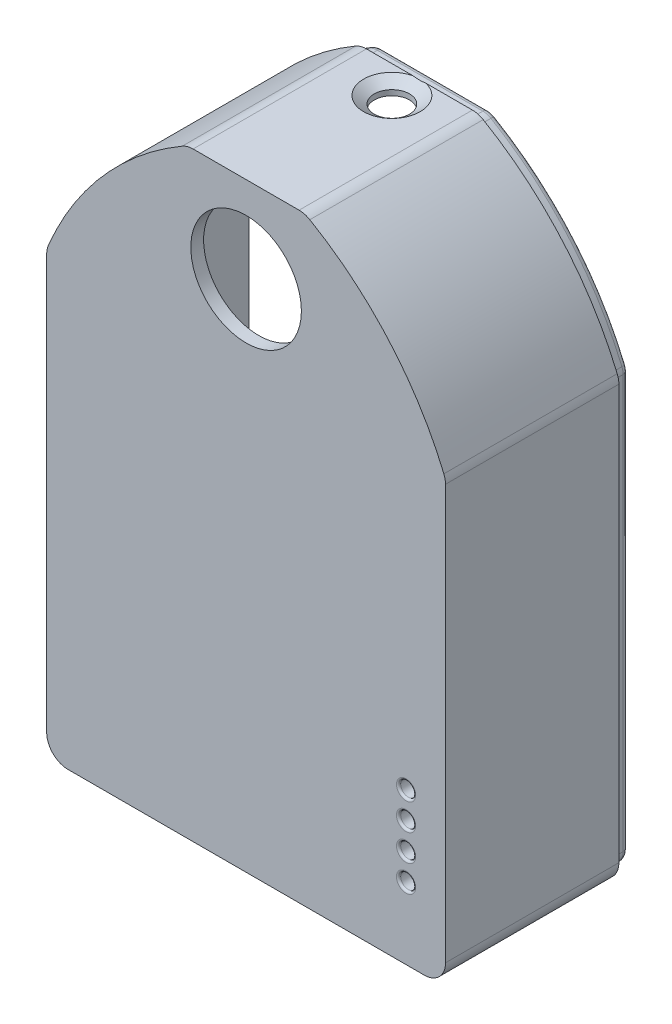
SolidWorks part; units mm, degrees
ref_plane "Front Plane" through (0, 0, 0) normal (0, 0, 1) x (1, 0, 0)
ref_plane "Top Plane" through (0, 0, 0) normal (0, 1, 0) x (1, 0, 0)
ref_plane "Right Plane" through (0, 0, 0) normal (1, 0, 0) x (0, 0, -1)
sketch "Sketch1" plane through (0, 0, 0) normal (0, 0, 1) x (1, 0, 0)
  circle A0 centre (-22.9417, 27.5534) radius 1.85
  circle A1 centre (-22.9417, -28.0566) radius 1.85
  circle A2 centre (30, 35.5) radius 1.1
  circle A3 centre (30, -35.5) radius 1.1
  dimension "D1" = 3.7
  dimension "D2" = 3.7
extrude "Extrude-Thin1" add sketch "Sketch1" along normal blind 5 thin thin type one direction wall 2.8
sketch "Sketch3" plane through (0, 0, 5) normal (0, 0, 1) x (1, 0, 0)
  line L0 (-37.4, -41.9) -> (37.4, -41.9)
  line L1 (37.4, -41.9) -> (37.4, 70.61)
  line L2 (37.4, 70.61) -> (-37.4, 70.61)
  line L3 (-37.4, 70.61) -> (-37.4, -41.9)
  line L4 (0, 70.61) -> (0, 40.61) construction
  line L5 (-37.4, 40.61) -> (37.4, 40.61) construction
  line L6 (-11, 70.61) -> (-11, 40.61) construction
  arc A0 (-37.4, 40.61) -> (-11, 70.61) centre (18.2718, 18.2348) cw
  arc A1 (37.4, 40.61) -> (11, 70.61) centre (-18.2718, 18.2348) ccw
  point P15 (0, 70.61)
  circle M7 centre (-22.9417, 27.5534) radius 4.65
  circle M8 centre (-22.9417, 27.5534) radius 1.85
  dimension "D6" = 60
  dimension "D1" = 2.4
  dimension "D2" = 3.4
  dimension "D3" = 3.4
  dimension "D4" = 2.4
  dimension "D5" = 11
  dimension "D7" = 30
extrude "Boss-Extrude2" add sketch "Sketch3" along normal blind 2.4 contours L1 A1 L2 A0 L3 L0 M7 | M7 M8 | M8 region at (0.2014, 10.5056, 5) region at (-27.4601, 27.5534, 5) region at (-22.9417, 27.5534, 5)
sketch "Sketch4" plane through (0, 0, 5) normal (0, 0, -1) x (-1, 0, 0)
  line L4 (-37.4, 40.61) -> (-37.4, -41.9)
  line L5 (-37.4, -41.9) -> (37.4, -41.9)
  line L6 (37.4, -41.9) -> (37.4, 40.61)
  line L7 (11, 70.61) -> (-11, 70.61)
  line L8 (-37.4, 40.61) -> (-37.4, -41.9)
  line L9 (-37.4, -41.9) -> (37.4, -41.9)
  line L10 (37.4, -41.9) -> (37.4, 40.61)
  line L11 (11, 70.61) -> (-11, 70.61)
  arc A2 (37.4, 40.61) -> (11, 70.61) centre (-18.2718, 18.2348) ccw
  arc A3 (-11, 70.61) -> (-37.4, 40.61) centre (18.2718, 18.2348) ccw
  arc A4 (37.4, 40.61) -> (11, 70.61) centre (-18.2718, 18.2348) ccw
  arc A5 (-11, 70.61) -> (-37.4, 40.61) centre (18.2718, 18.2348) ccw
  dimension "D1" = 0
extrude "Extrude-Thin2" add sketch "Sketch4" along normal up to surface (30.11 mm away) thin thin type one direction reverse wall 2.4
sketch "Sketch5" plane through (0, 0, 7.4) normal (0, 0, 1) x (1, 0, 0)
  circle A0 centre (0, 54.4311) radius 10.3689
extrude "Cut-Extrude1" cut sketch "Sketch5" against normal blind 2.4
sketch "Sketch6" plane through (0, 0, -25.11) normal (0, 0, -1) x (-1, 0, 0)
  line L0 (35, -39.5) -> (-35, -39.5) construction
  line L1 (35, 40.1408) -> (35, -39.5) construction
  line L2 (-10.368, 68.21) -> (10.368, 68.21) construction
  line L3 (-35, -39.5) -> (-35, 40.1408) construction
  line L4 (35, -39.5) -> (-35, -39.5)
  line L5 (35, 40.1408) -> (35, -39.5)
  line L6 (-10.368, 68.21) -> (10.368, 68.21)
  line L7 (-35, -39.5) -> (-35, 40.1408)
  arc A0 (35, 40.1408) -> (10.368, 68.21) centre (-18.2718, 18.2348) ccw construction
  arc A1 (-10.368, 68.21) -> (-35, 40.1408) centre (18.2718, 18.2348) ccw construction
  arc A2 (35, 40.1408) -> (10.368, 68.21) centre (-18.2718, 18.2348) ccw
  arc A3 (-10.368, 68.21) -> (-35, 40.1408) centre (18.2718, 18.2348) ccw
extrude "Extrude-Thin3" add sketch "Sketch6" along normal up to surface (3 mm away) thin thin type one direction wall 1.2
sketch "Sketch7" plane through (0, -41.9, 0) normal (0, -1, 0) x (1, 0, 0)
  line L0 (-34, -1.51) -> (34, -1.51) construction
  line L1 (-6.0348, -7.6386) -> (3.7281, -7.6386)
  line L2 (-6.0348, -7.6386) -> (-6.0348, -2.31)
  line L3 (-6.0348, -2.31) -> (3.7281, -2.31)
  line L4 (3.7281, -7.6386) -> (3.7281, -2.31)
  line L17 (18, -0.615) -> (21.22, -0.615)
  line L18 (14.78, -0.615) -> (18, -0.615)
  line L19 (12.73, 2.095) -> (12.73, 1.435)
  line L20 (18, 4.145) -> (14.78, 4.145)
  line L21 (21.22, 4.145) -> (18, 4.145)
  line L22 (23.27, 1.435) -> (23.27, 2.095)
  line L23 (18, -0.615) -> (21.22, -0.615)
  line L24 (14.78, -0.615) -> (18, -0.615)
  line L25 (12.73, 2.095) -> (12.73, 1.435)
  line L26 (18, 4.145) -> (14.78, 4.145)
  line L27 (21.22, 4.145) -> (18, 4.145)
  line L28 (23.27, 1.435) -> (23.27, 2.095)
  arc A8 (12.73, 1.435) -> (14.78, -0.615) centre (14.78, 1.435) ccw
  arc A9 (14.78, 4.145) -> (12.73, 2.095) centre (14.78, 2.095) ccw
  arc A10 (21.22, -0.615) -> (23.27, 1.435) centre (21.22, 1.435) ccw
  arc A11 (23.27, 2.095) -> (21.22, 4.145) centre (21.22, 2.095) ccw
  arc A12 (12.73, 1.435) -> (14.78, -0.615) centre (14.78, 1.435) ccw
  arc A13 (14.78, 4.145) -> (12.73, 2.095) centre (14.78, 2.095) ccw
  arc A14 (21.22, -0.615) -> (23.27, 1.435) centre (21.22, 1.435) ccw
  arc A15 (23.27, 2.095) -> (21.22, 4.145) centre (21.22, 2.095) ccw
  dimension "D1" = 0.8
  dimension "D2" = 0.8
extrude "Cut-Extrude2" cut sketch "Sketch7" against normal blind 2.4
sketch "Sketch10" plane through (-37.4, 0, 0) normal (-1, 0, 0) x (0, 0, 1)
  line L0 (-1.6477, 0.8133) -> (1.2523, 0.8133) construction
  line L1 (3.185, -7.85) -> (-0.1977, -7.85)
  line L2 (3.185, -7.85) -> (3.185, 0.8133)
  line L3 (3.185, 0.8133) -> (-0.1977, 0.8133)
  line L4 (-0.1977, -7.85) -> (-0.1977, 0.8133)
  line L5 (-0.1977, -3.5184) -> (3.185, -3.5184) construction
  line L6 (-0.1977, 0.0133) -> (3.185, 0.0133)
  line L7 (-0.1977, -1.7184) -> (3.185, -1.7184)
  line L8 (-0.1977, -2.7184) -> (3.185, -2.7184)
  line L9 (-0.1977, -7.05) -> (3.185, -7.05)
  line L10 (-0.1977, -5.3184) -> (3.185, -5.3184)
  line L11 (-0.1977, -4.3184) -> (3.185, -4.3184)
  dimension "D1" = 0.8
  dimension "D2" = 0.8
  dimension "D3" = 1
extrude "Cut-Extrude4" cut sketch "Sketch10" against normal blind 2.4 contours L4 L7 L2 L6 | L4 L5 L2 L8 | L5 L4 L11 L2 | L10 L4 L9 L2 region at (-37.4, -6.1842, 1.4937) region at (-37.4, -3.9184, 1.4937) region at (-37.4, -3.1184, 1.4937) region at (-37.4, -0.8525, 1.4937)
sketch "Sketch11" plane through (0, 0, 7.4) normal (0, 0, 1) x (1, 0, 0)
  circle A0 centre (30, -28.5) radius 1.4
  circle A1 centre (30, -23.5) radius 1.4
  circle A2 centre (30, -18.5) radius 1.4
  circle A3 centre (30, -13.5) radius 1.4
  dimension "D1" = 2.8
extrude "Cut-Extrude5" cut sketch "Sketch11" against normal blind 2.4
fillet "Fillet2" radius 0.4 40 edges at (-35, -7.05, 1.4937) (-37.4, -7.05, 1.4937) (-35, -5.3184, 1.4937) (-37.4, -5.3184, 1.4937) (-35, -4.3184, 1.4937) (-37.4, -4.3184, 1.4937) (-35, -2.7184, 1.4937) (-37.4, -2.7184, 1.4937) (-35, -1.7184, 1.4937) (-37.4, -1.7184, 1.4937) (-35, 0.0133, 1.4937) (-37.4, 0.0133, 1.4937) (-36.2, 0.0133, -0.1977) (-35, -0.8525, -0.1977) (-36.2, -1.7184, -0.1977) (-37.4, -0.8525, -0.1977) (-36.2, -2.7184, -0.1977) (-35, -3.5184, -0.1977) (-36.2, -4.3184, -0.1977) (-37.4, -3.5184, -0.1977) (-36.2, -5.3184, -0.1977) (-35, -6.1842, -0.1977) (-36.2, -7.05, -0.1977) (-37.4, -6.1842, -0.1977) (-36.2, -7.05, 3.185) (-35, -6.1842, 3.185) (-36.2, -5.3184, 3.185) (-37.4, -6.1842, 3.185) (-36.2, -4.3184, 3.185) (-35, -3.5184, 3.185) (-36.2, -2.7184, 3.185) (-37.4, -3.5184, 3.185) (-36.2, -1.7184, 3.185) (-35, -0.8525, 3.185) (-36.2, 0.0133, 3.185) (-37.4, -0.8525, 3.185) (31.4, -28.5, 7.4) (31.4, -23.5, 7.4) (31.4, -18.5, 7.4) (31.4, -13.5, 7.4)
fillet "Fillet3" radius 2 12 edges at (22.6696, -41.9, 3.5446) (23.27, -41.9, 1.765) (22.6696, -41.9, -0.0146) (18, -41.9, -0.615) (13.3304, -41.9, -0.0146) (12.73, -41.9, 1.765) (13.3304, -41.9, 3.5446) (3.7281, -41.9, -4.9743) (-1.1534, -41.9, -7.6386) (-6.0348, -41.9, -4.9743) (-1.1534, -41.9, -2.31) (18, -41.9, 4.145)
sketch "Sketch12" plane through (0, 70.61, 0) normal (0, 1, 0) x (1, 0, 0)
  circle A0 centre (0, 19.945) radius 3.3
  dimension "D1" = 6.6
extrude "Cut-Extrude6" cut sketch "Sketch12" against normal blind 2.4
chamfer "Chamfer1" distance 2 angle 35 1 edges at (-3.3, 70.61, -19.945) first distance on face at (-3.3, 70.61, -19.945)
fillet "Fillet4" radius 4 6 edges at (37.4, -41.9, -8.855) (-37.4, -41.9, -8.855) (-37.4, 40.61, -8.855) (-11, 70.61, -8.855) (11, 70.61, -8.855) (37.4, 40.61, -8.855)
fillet "Fillet5" radius 3 6 edges at (-36.2, 40.3767, -26.61) (-10.6857, 69.41, -26.61) (10.6857, 69.41, -26.61) (36.2, 40.3767, -26.61) (-36.2, -40.7, -26.61) (36.2, -40.7, -26.61)
fillet "Fillet6" radius 1 12 edges at (35.3213, -39.8213, -28.11) (0, -40.7, -28.11) (-35.3213, -39.8213, -28.11) (-36.2, 1.0411, -28.11) (-36.1413, 40.3731, -28.11) (-25.9665, 56.9699, -28.11) (-10.6689, 69.3057, -28.11) (0, 69.41, -28.11) (10.6689, 69.3057, -28.11) (25.9665, 56.9699, -28.11) (36.1413, 40.3731, -28.11) (36.2, 1.0411, -28.11)
equation "\"D1@Sketch1\"=\"Sleeve@Box_Admin.Assembly\""
equation "\"D2@Sketch1\"=\"Sleeve@Box_Admin.Assembly\""
equation "\"D1@Sketch3\"=\"Wall thickness@Box_Admin.Assembly\""
equation "\"D2@Sketch3\"=1+\"Wall thickness@Box_Admin.Assembly\""
equation "\"D3@Sketch3\"=1+\"Wall thickness@Box_Admin.Assembly\""
equation "\"D4@Sketch3\"=\"Wall thickness@Box_Admin.Assembly\""
equation "\"D1@Boss-Extrude2\"=\"Wall thickness@Box_Admin.Assembly\""
equation "\"D5@Extrude-Thin2\"=\"Wall thickness@Box_Admin.Assembly\""
equation "\"D5@Extrude-Thin3\"=\"Groove thickness@Box_Admin.Assembly\""
equation "\"D1@Cut-Extrude2\"=\"Wall thickness@Box_Admin.Assembly\""
equation "\"D1@Cut-Extrude5\"=\"Wall thickness@Box_Admin.Assembly\""
equation "\"D1@Cut-Extrude4\"=\"Wall thickness@Box_Admin.Assembly\""
equation "\"D1@Cut-Extrude6\"=\"Wall thickness@Box_Admin.Assembly\""
